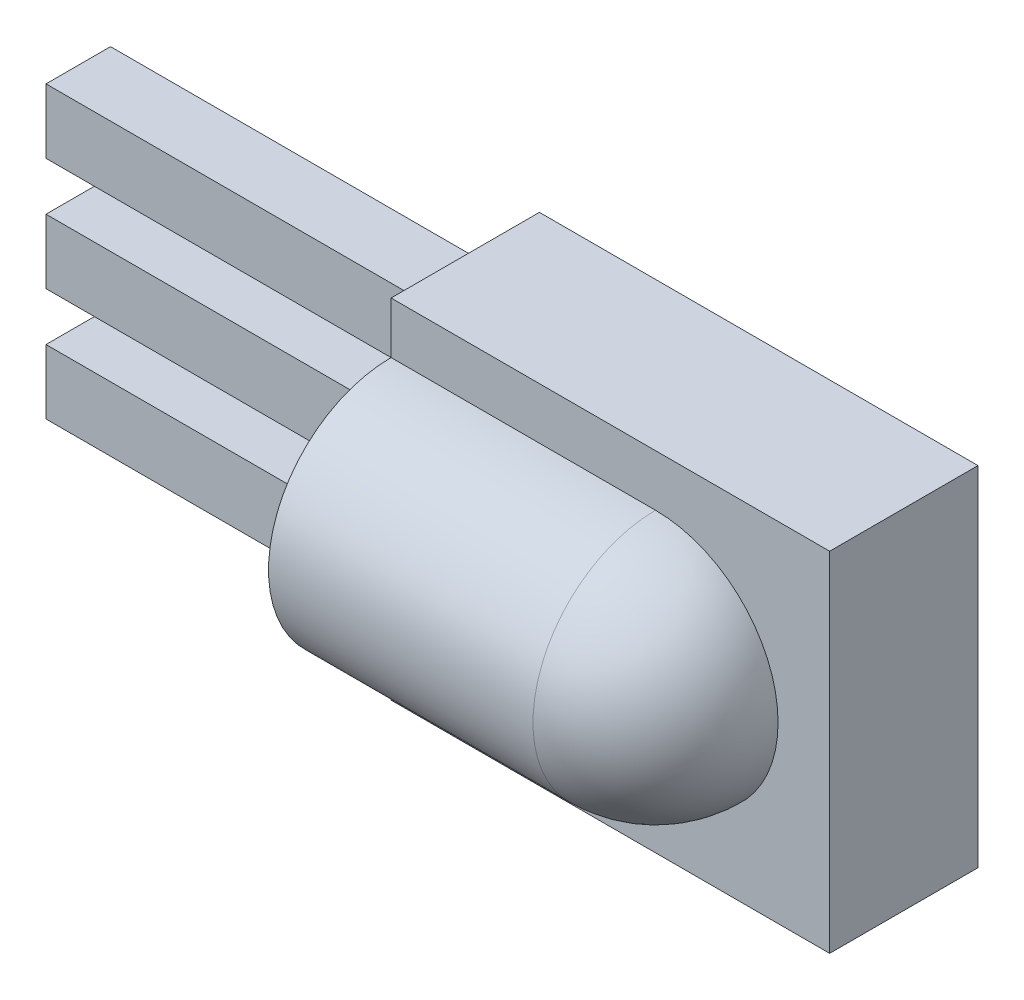
SolidWorks part; units mm, degrees
ref_plane "Plan de face" through (0, 0, 0) normal (0, 0, 1) x (1, 0, 0)
ref_plane "Plan de dessus" through (0, 0, 0) normal (0, 1, 0) x (1, 0, 0)
ref_plane "Plan de droite" through (0, 0, 0) normal (1, 0, 0) x (0, 0, -1)
sketch "Esquisse1" plane through (0, 0, 0) normal (0, 0, 1) x (1, 0, 0)
  line L1 (0, 0) -> (6.8, 0)
  line L2 (0, 0) -> (0, 5.4)
  line L3 (0, 5.4) -> (6.8, 5.4)
  line L4 (6.8, 0) -> (6.8, 5.4)
  dimension "D1" = 5.4
  dimension "D2" = 6.8
extrude "Boss.-Extru.1" add sketch "Esquisse1" along normal blind 2.3
sketch "Esquisse2" plane through (0, 0, 0) normal (-1, 0, 0) x (0, 0, 1)
  line L0 (2.3, 5.4) -> (2.3, 0) construction
  circle A0 centre (2.3, 2.7) radius 1.9
extrude "Boss.-Extru.2" add sketch "Esquisse2" against normal blind 6
fillet "Congé1" radius 1.9 1 edges at (6, 2.7, 4.2)
sketch "Esquisse3" plane through (0, 0, 0) normal (-1, 0, 0) x (0, 0, 1)
  line L0 (1.65, 3.95) -> (1.65, 4.95)
  line L1 (1.65, 2.2) -> (0.65, 2.2)
  line L2 (1.65, 2.2) -> (1.65, 3.2)
  line L3 (1.65, 3.2) -> (0.65, 3.2)
  line L4 (0.65, 2.2) -> (0.65, 3.2)
  line L5 (1.65, 2.2) -> (0.65, 3.2) construction
  line L6 (1.65, 3.2) -> (0.65, 2.2) construction
  line L7 (1.65, 3.95) -> (0.65, 3.95)
  line L8 (0.65, 3.95) -> (0.65, 4.95)
  line L9 (1.65, 4.95) -> (0.65, 4.95)
  line L10 (1.65, 0.45) -> (1.65, 1.45)
  line L11 (1.65, 0.45) -> (0.65, 0.45)
  line L12 (0.65, 0.45) -> (0.65, 1.45)
  line L13 (1.65, 1.45) -> (0.65, 1.45)
  point P0 (1.15, 2.7)
  dimension "D1" = 1
  dimension "D2" = 1
  dimension "D3" = 2
  dimension "D4" = 2
extrude "Boss.-Extru.3" add sketch "Esquisse3" along normal blind 6
